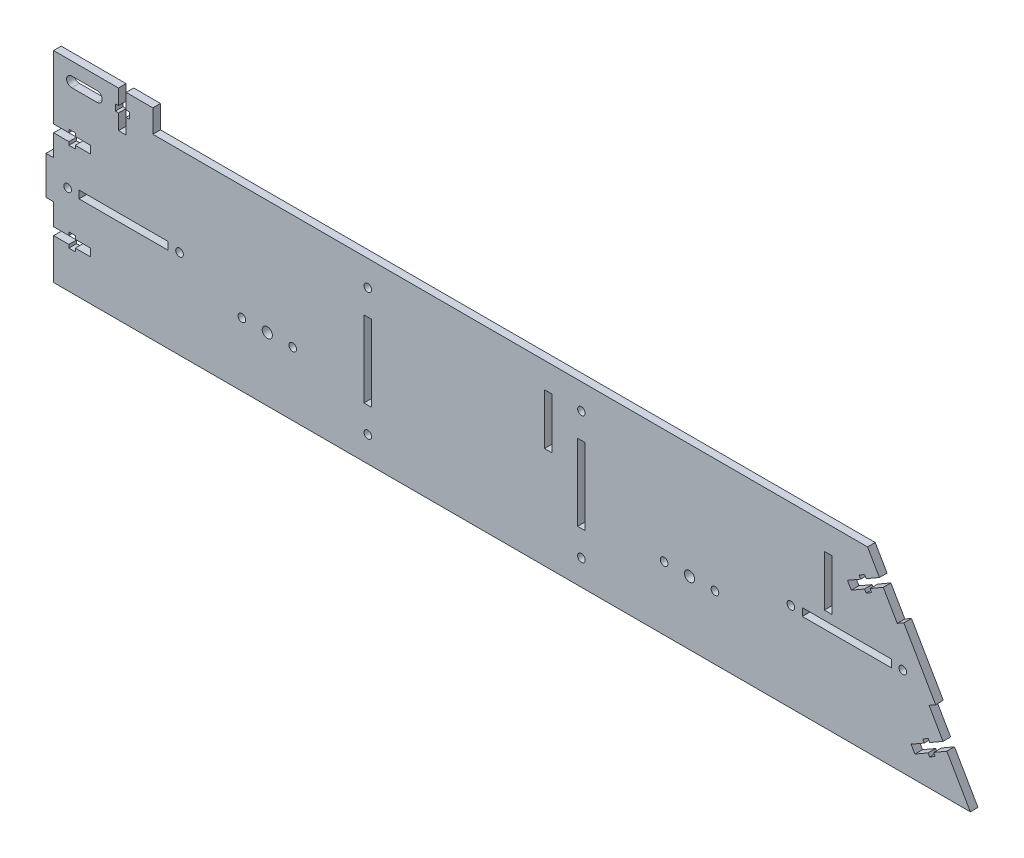
SolidWorks part; units mm, degrees
ref_plane "Спереди" through (0, 0, 0) normal (0, 0, 1) x (1, 0, 0)
ref_plane "Сверху" through (0, 0, 0) normal (0, 1, 0) x (1, 0, 0)
ref_plane "Справа" through (0, 0, 0) normal (1, 0, 0) x (0, 0, -1)
sketch "Эскиз1" plane through (0, 0, 0) normal (0, 0, 1) x (1, 0, 0)
  line L0 (320, 70) -> (360.4145, 0)
  line L2 (0, 0) -> (0, 70)
  line L3 (0, 70) -> (320, 70)
  line L5 (0, 0) -> (360.4145, 0)
  circle A0 centre (84, 25) radius 2
  circle A1 centre (250, 25) radius 2
  circle A2 centre (84, 25) radius 10 construction
  circle A3 centre (94, 25) radius 1.5
  circle A4 centre (74, 25) radius 1.5
  circle A5 centre (240, 25) radius 1.5
  circle A6 centre (260, 25) radius 1.5
  circle A7 centre (250, 25) radius 10 construction
  dimension "D4" = 4
  dimension "D8" = 20
  dimension "D9" = 3
  dimension "D10" = 80.829
  dimension "D1" = 320
  dimension "D2" = 70
  dimension "D3" = 60
  dimension "D5" = 25
  dimension "D6" = 166
  dimension "D7" = 84
extrude "Бобышка-Вытянуть1" add sketch "Эскиз1" along normal blind 3
sketch "Эскиз2" plane through (0, 70, 0) normal (0, 1, 0) x (1, 0, 0)
  line L0 (320, -3) -> (0, -3) construction
  line L1 (301, -3) -> (282, -3)
  line L2 (301, -3) -> (301, 0)
  line L3 (301, 0) -> (282, 0)
  line L4 (282, -3) -> (282, 0)
  line L5 (320, 0) -> (0, 0) construction
  dimension "D1" = 19
  dimension "D2" = 19
extrude "Бобышка-Вытянуть2" add sketch "Эскиз2" along normal blind 3
pattern_linear "Линейный массив1" count 9 spacing 28 along (-1, 0, 0) of "Бобышка-Вытянуть2"
sketch "Эскиз3" plane through (0, 0, 3) normal (0, 0, 1) x (1, 0, 0)
  line L0 (198, 73) -> (217, 73) construction
  line L1 (206, 50) -> (209, 50)
  line L2 (206, 50) -> (206, 20)
  line L3 (206, 20) -> (209, 20)
  line L4 (209, 50) -> (209, 20)
  line L5 (206, 50) -> (209, 20) construction
  line L6 (206, 20) -> (209, 50) construction
  line L7 (0, 70) -> (0, 0) construction
  line L8 (114, 73) -> (133, 73) construction
  line L9 (122, 50) -> (125, 50)
  line L10 (122, 50) -> (122, 20)
  line L11 (122, 20) -> (125, 20)
  line L12 (125, 50) -> (125, 20)
  line L13 (122, 50) -> (125, 20) construction
  line L14 (122, 20) -> (125, 50) construction
  point P0 (207.5, 35)
  point P9 (207.5, 73)
  point P10 (123.5, 73)
  point P13 (0, 35)
  point P14 (123.5, 35)
  point P19 (123.5, 20)
  point P21 (207.5, 20)
  dimension "D3" = 123.5
  dimension "D1" = 30
  dimension "D2" = 3
  dimension "D4" = 84
extrude "Вырез-Вытянуть1" cut sketch "Эскиз3" against normal blind 3
sketch "Эскиз4" plane through (0, 0, 3) normal (0, 0, 1) x (1, 0, 0)
  line L0 (0, 70) -> (0, 0) construction
  line L1 (294.3412, 36.5) -> (329.3412, 36.5)
  line L2 (294.3412, 36.5) -> (294.3412, 33.5)
  line L3 (294.3412, 33.5) -> (329.3412, 33.5)
  line L4 (329.3412, 36.5) -> (329.3412, 33.5)
  line L5 (294.3412, 36.5) -> (329.3412, 33.5) construction
  line L6 (294.3412, 33.5) -> (329.3412, 36.5) construction
  line L7 (10, 36.5) -> (45, 36.5)
  line L8 (10, 36.5) -> (10, 33.5)
  line L9 (10, 33.5) -> (45, 33.5)
  line L10 (45, 36.5) -> (45, 33.5)
  line L11 (10, 36.5) -> (45, 33.5) construction
  line L12 (10, 33.5) -> (45, 36.5) construction
  line L14 (329.3412, 36.5) -> (339.3412, 36.5) construction
  line L15 (360.4145, 0) -> (320, 70) construction
  circle A0 centre (84, 25) radius 35 construction
  point P0 (311.8412, 35)
  point P5 (27.5, 35)
  point P15 (0, 35)
  point P18 (340.2073, 35)
  dimension "D5" = 70
  dimension "D1" = 35
  dimension "D2" = 3
  dimension "D3" = 10
  dimension "D4" = 10
  dimension "D6" = 40.4145
  dimension "D7" = 284.3412
extrude "Вырез-Вытянуть2" cut sketch "Эскиз4" against normal blind 3
sketch "Эскиз5" plane through (0, 0, 3) normal (0, 0, 1) x (1, 0, 0)
  line L0 (125, 50) -> (122, 50) construction
  line L1 (209, 50) -> (206, 50) construction
  line L2 (294.3412, 36.5) -> (294.3412, 33.5) construction
  line L3 (10, 36.5) -> (10, 33.5) construction
  circle A0 centre (5.5, 35) radius 1.5
  circle A1 centre (49.5, 35) radius 1.5
  circle A2 centre (123.5, 60) radius 1.5
  circle A3 centre (123.5, 10) radius 1.5
  circle A4 centre (207.5, 60) radius 1.5
  circle A5 centre (207.5, 10) radius 1.5
  circle A6 centre (289.8412, 35) radius 1.5
  circle A7 centre (333.8412, 35) radius 1.5
  point P20 (123.5, 50)
  point P29 (207.5, 50)
  point P34 (294.3412, 35)
  point P42 (10, 35)
  dimension "D1" = 3
  dimension "D2" = 10
  dimension "D3" = 10
  dimension "D4" = 4.5
  dimension "D5" = 4.5
  dimension "D6" = 4.5
  dimension "D7" = 4.5
extrude "Вырез-Вытянуть3" cut sketch "Эскиз5" against normal blind 3
sketch "Эскиз6" plane through (0, 0, 3) normal (0, 0, 1) x (1, 0, 0)
  line L0 (0, 54) -> (6, 54)
  line L1 (6, 54) -> (6, 55.25)
  line L2 (6, 55.25) -> (8.5, 55.25)
  line L3 (8.5, 55.25) -> (8.5, 54)
  line L4 (8.5, 54) -> (14.5, 54)
  line L5 (14.5, 54) -> (14.5, 51)
  line L6 (14.5, 51) -> (8.5, 51)
  line L7 (8.5, 51) -> (8.5, 49.75)
  line L8 (8.5, 49.75) -> (6, 49.75)
  line L9 (6, 49.75) -> (6, 51)
  line L10 (6, 51) -> (0, 51)
  line L13 (0, 19) -> (6, 19)
  line L14 (6, 19) -> (6, 20.25)
  line L15 (6, 20.25) -> (8.5, 20.25)
  line L16 (8.5, 20.25) -> (8.5, 19)
  line L17 (8.5, 19) -> (14.5, 19)
  line L18 (14.5, 19) -> (14.5, 16)
  line L19 (14.5, 16) -> (8.5, 16)
  line L20 (8.5, 16) -> (8.5, 14.75)
  line L21 (8.5, 14.75) -> (6, 14.75)
  line L22 (6, 14.75) -> (6, 16)
  line L23 (6, 16) -> (0, 16)
  line L24 (0, 70) -> (0, 0) construction
  line L25 (0, 0) -> (360.4145, 0) construction
  line L26 (0, 54) -> (0, 51)
  line L27 (0, 19) -> (0, 16)
  point P12 (7.25, 49.75)
  point P28 (7.25, 14.75)
  point P31 (14.5, 52.5)
  point P32 (14.5, 17.5)
  dimension "D1" = 2.5
  dimension "D2" = 3
  dimension "D3" = 5.5
  dimension "D4" = 6
  dimension "D5" = 6
  dimension "D6" = 2.5
  dimension "D7" = 3
  dimension "D8" = 5.5
  dimension "D9" = 6
  dimension "D10" = 6
  dimension "D11" = 35
  dimension "D12" = 17.5
extrude "Вырез-Вытянуть4" cut sketch "Эскиз6" against normal blind 3
sketch "Эскиз7" plane through (0, 0, 3) normal (0, 0, 1) x (1, 0, 0)
  line L0 (324.6645, 61.9208) -> (319.4684, 58.9208)
  line L1 (319.4684, 58.9208) -> (318.8434, 60.0033)
  line L2 (318.8434, 60.0033) -> (316.6783, 58.7533)
  line L3 (316.6783, 58.7533) -> (317.3033, 57.6708)
  line L4 (317.3033, 57.6708) -> (312.1072, 54.6708)
  line L5 (312.1072, 54.6708) -> (313.6072, 52.0727)
  line L6 (313.6072, 52.0727) -> (318.8033, 55.0727)
  line L7 (318.8033, 55.0727) -> (319.4283, 53.9902)
  line L8 (319.4283, 53.9902) -> (321.5934, 55.2402)
  line L9 (321.5934, 55.2402) -> (320.9684, 56.3227)
  line L10 (320.9684, 56.3227) -> (326.1645, 59.3227)
  line L11 (326.1645, 59.3227) -> (324.6645, 61.9208)
  line L12 (349.6645, 18.6195) -> (344.4684, 15.6195)
  line L13 (344.4684, 15.6195) -> (343.8434, 16.7021)
  line L14 (343.8434, 16.7021) -> (341.6783, 15.4521)
  line L15 (341.6783, 15.4521) -> (342.3033, 14.3695)
  line L16 (342.3033, 14.3695) -> (337.1072, 11.3695)
  line L17 (337.1072, 11.3695) -> (338.6072, 8.7715)
  line L18 (338.6072, 8.7715) -> (343.8033, 11.7715)
  line L19 (343.8033, 11.7715) -> (344.4283, 10.6889)
  line L20 (344.4283, 10.6889) -> (346.5934, 11.9389)
  line L21 (346.5934, 11.9389) -> (345.9684, 13.0215)
  line L22 (345.9684, 13.0215) -> (351.1645, 16.0215)
  line L23 (351.1645, 16.0215) -> (349.6645, 18.6195)
  line L24 (360.4145, 0) -> (320, 70) construction
  point P24 (350.4145, 17.3205)
  dimension "D1" = 6
  dimension "D2" = 2.5
  dimension "D3" = 3
  dimension "D4" = 5.5
  dimension "D5" = 6
  dimension "D6" = 2.5
  dimension "D7" = 3
  dimension "D8" = 5.5
  dimension "D9" = 50
  dimension "D10" = 20
extrude "Вырез-Вытянуть5" cut sketch "Эскиз7" against normal blind 3
sketch "Эскиз8" plane through (0, 70, 0) normal (0, 1, 0) x (1, 0, 0)
  line L0 (58, -3) -> (0, -3) construction
  line L1 (0, 0) -> (39, 0)
  line L2 (0, 0) -> (0, -3)
  line L3 (0, -3) -> (39, -3)
  line L4 (39, 0) -> (39, -3)
  dimension "D1" = 39
extrude "Бобышка-Вытянуть3" add sketch "Эскиз8" along normal blind 9
sketch "Эскиз11" plane through (270.3109, 156.0641, 0) normal (0.866, 0.5, 0) x (0, 0, -1)
  line L0 (-3, -158.7073) -> (-3, -111.7073) construction
  line L1 (-3, -147.7073) -> (0, -147.7073)
  line L2 (-3, -147.7073) -> (-3, -122.7073)
  line L3 (-3, -122.7073) -> (0, -122.7073)
  line L4 (0, -147.7073) -> (0, -122.7073)
  line L5 (0, -158.7073) -> (0, -111.7073) construction
  point P9 (-3, -135.2073)
  point P10 (-3, -135.2073)
  dimension "D1" = 25
extrude "Бобышка-Вытянуть5" add sketch "Эскиз11" along normal blind 3
sketch "Эскиз12" plane through (0, 0, 0) normal (-1, 0, 0) x (0, 0, 1)
  line L0 (0, 51) -> (0, 19) construction
  line L1 (0, 27.5) -> (3, 27.5)
  line L2 (0, 27.5) -> (0, 42.5)
  line L3 (0, 42.5) -> (3, 42.5)
  line L4 (3, 27.5) -> (3, 42.5)
  line L5 (3, 51) -> (3, 19) construction
  point P9 (0, 35)
  point P10 (0, 35)
  dimension "D1" = 15
extrude "Бобышка-Вытянуть6" add sketch "Эскиз12" along normal blind 3
sketch "Эскиз13" plane through (0, 0, 3) normal (0, 0, 1) x (1, 0, 0)
  line L1 (58, 70) -> (301, 70)
  line L2 (58, 70) -> (58, 73)
  line L3 (58, 73) -> (301, 73)
  line L4 (301, 70) -> (301, 73)
extrude "Вырез-Вытянуть7" cut sketch "Эскиз13" against normal blind 3
sketch "Эскиз14" plane through (0, 0, 3) normal (0, 0, 1) x (1, 0, 0)
  line L1 (196, 60) -> (193, 60)
  line L2 (196, 60) -> (196, 40)
  line L3 (196, 40) -> (193, 40)
  line L4 (193, 60) -> (193, 40)
  line L5 (0, 0) -> (360.4145, 0) construction
  line L6 (306, 60) -> (303, 60)
  line L7 (306, 60) -> (306, 40)
  line L8 (306, 40) -> (303, 40)
  line L9 (303, 60) -> (303, 40)
  dimension "D1" = 3
  dimension "D2" = 40
  dimension "D3" = 10
  dimension "D4" = 20
  dimension "D5" = 3
  dimension "D7" = 20
  dimension "D8" = 110
extrude "Вырез-Вытянуть8" cut sketch "Эскиз14" against normal blind 10
sketch "Эскиз15" plane through (0, 0, 3) normal (0, 0, 1) x (1, 0, 0)
  line L0 (25.5, 79) -> (25.5, 73)
  line L1 (25.5, 73) -> (24.25, 73)
  line L2 (24.25, 73) -> (24.25, 70.5)
  line L3 (24.25, 70.5) -> (25.5, 70.5)
  line L4 (25.5, 70.5) -> (25.5, 64.5)
  line L5 (25.5, 64.5) -> (28.5, 64.5)
  line L6 (28.5, 64.5) -> (28.5, 70.5)
  line L7 (28.5, 70.5) -> (29.75, 70.5)
  line L8 (29.75, 70.5) -> (29.75, 73)
  line L9 (29.75, 73) -> (28.5, 73)
  line L10 (28.5, 73) -> (28.5, 79)
  line L11 (28.5, 79) -> (25.5, 79)
  line L12 (0, 79) -> (39, 79) construction
  point P15 (27, 79)
  dimension "D1" = 6
  dimension "D2" = 3
  dimension "D3" = 5.5
  dimension "D4" = 2.5
  dimension "D5" = 30
extrude "Вырез-Вытянуть9" cut sketch "Эскиз15" against normal blind 3
sketch "Эскиз16" plane through (0, 0, 3) normal (0, 0, 1) x (1, 0, 0)
  line L0 (7.0949, 71.8989) -> (17.0949, 71.8989) construction
  line L1 (7.0949, 73.8989) -> (17.0949, 73.8989)
  line L2 (7.0949, 69.8989) -> (17.0949, 69.8989)
  arc A0 (7.0949, 73.8989) -> (7.0949, 69.8989) centre (7.0949, 71.8989) ccw
  arc A1 (17.0949, 69.8989) -> (17.0949, 73.8989) centre (17.0949, 71.8989) ccw
  point P2 (12.0949, 71.8989)
  point P7 (12.0949, 71.8989)
  dimension "D2" = 2
  dimension "D1" = 10
extrude "Вырез-Вытянуть10" cut sketch "Эскиз16" against normal blind 10
